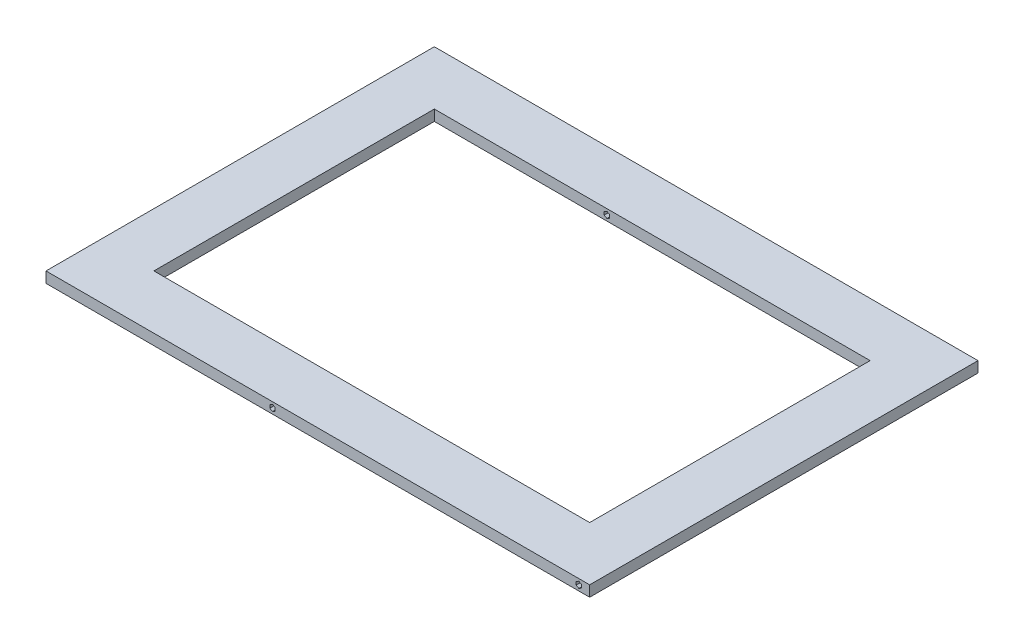
SolidWorks part; units mm, degrees
ref_plane "Front Plane" through (0, 0, 0) normal (0, 0, 1) x (1, 0, 0)
ref_plane "Top Plane" through (0, 0, 0) normal (0, 1, 0) x (1, 0, 0)
ref_plane "Right Plane" through (0, 0, 0) normal (1, 0, 0) x (0, 0, -1)
sketch "Sketch1" plane through (0, 0, 0) normal (0, 0, 1) x (1, 0, 0)
  line L1 (-126, -2.5) -> (126, -2.5)
  line L2 (-126, -2.5) -> (-126, 2.5)
  line L3 (-126, 2.5) -> (126, 2.5)
  line L4 (126, -2.5) -> (126, 2.5)
  line L5 (-126, -2.5) -> (126, 2.5) construction
  line L6 (-126, 2.5) -> (126, -2.5) construction
  point P0 (0, 0)
  dimension "D1" = 252
  dimension "D2" = 5
extrude "Boss-Extrude1" add sketch "Sketch1" along normal blind 90 and the other way blind 90
sketch "Sketch2" plane through (0, 0, 90) normal (0, 0, 1) x (1, 0, 0)
  line L0 (-126, 2.5) -> (-126, -2.5) construction
  line L1 (-21, 1.4434) -> (-22.25, 0.7217)
  line L2 (-22.25, 0.7217) -> (-22.25, -0.7217)
  line L3 (-22.25, -0.7217) -> (-21, -1.4434)
  line L4 (-21, -1.4434) -> (-19.75, -0.7217)
  line L5 (-19.75, -0.7217) -> (-19.75, 0.7217)
  line L6 (-19.75, 0.7217) -> (-21, 1.4434)
  line L14 (126, -2.5) -> (126, 2.5) construction
  line L15 (121, 1.4434) -> (119.75, 0.7217)
  line L16 (119.75, 0.7217) -> (119.75, -0.7217)
  line L17 (119.75, -0.7217) -> (121, -1.4434)
  line L18 (121, -1.4434) -> (122.25, -0.7217)
  line L19 (122.25, -0.7217) -> (122.25, 0.7217)
  line L20 (122.25, 0.7217) -> (121, 1.4434)
  circle A0 centre (-21, 0) radius 1.25 construction
  circle A1 centre (121, 0) radius 1.25 construction
  point P11 (-126, 0)
  point P14 (0, 0)
  point P22 (126, 0)
  dimension "D1" = 2.5
  dimension "D3" = 2.5
  dimension "D4" = 5
  dimension "D2" = 105
extrude "Cut-Extrude1" cut sketch "Sketch2" against normal through all
sketch "Sketch5" plane through (0, 2.5, 0) normal (0, 1, 0) x (1, 0, 0)
  line L8 (-101, 65) -> (-101, -65)
  line L9 (-101, -65) -> (101, -65)
  line L10 (101, -65) -> (101, 65)
  line L11 (101, 65) -> (-101, 65)
  line L12 (-101, 65) -> (-101, -65)
  line L13 (-101, -65) -> (101, -65)
  line L14 (101, -65) -> (101, 65)
  line L15 (101, 65) -> (-101, 65)
  dimension "D1" = 25
extrude "Cut-Extrude3" cut sketch "Sketch5" against normal through all
